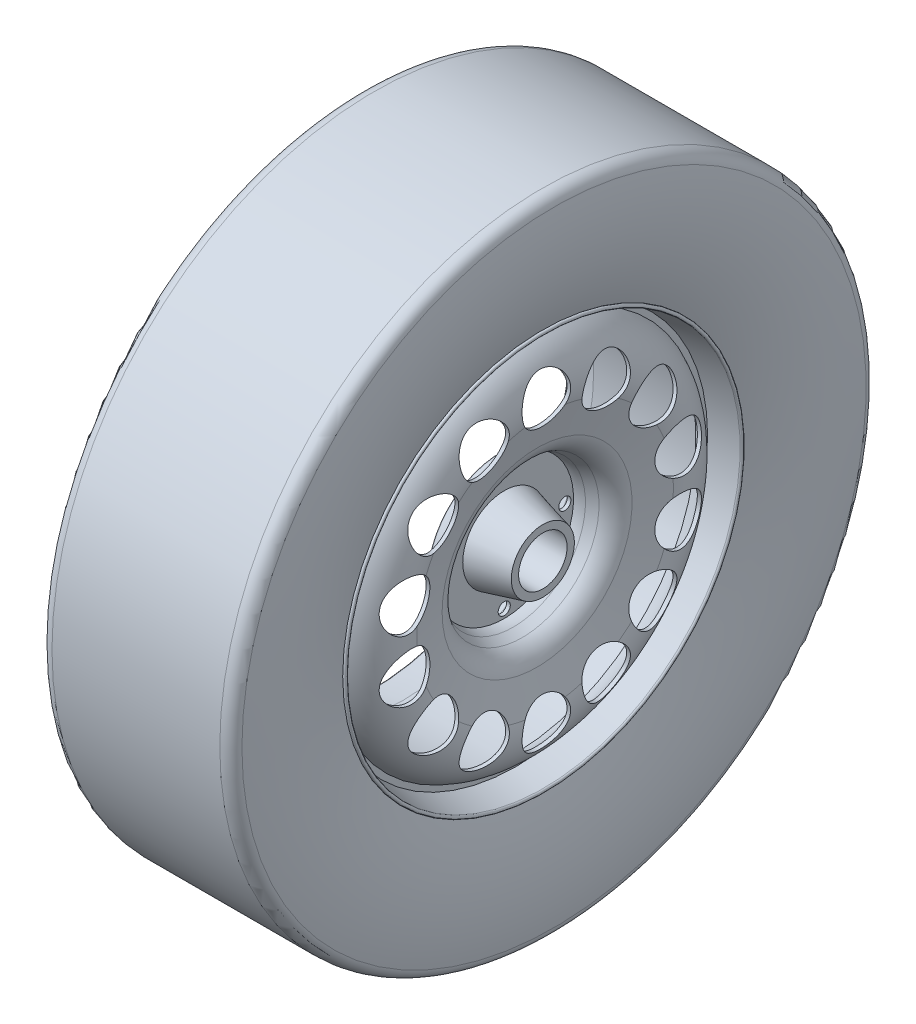
SolidWorks part; units mm, degrees
ref_plane "Front Plane" through (0, 0, 0) normal (0, 0, 1) x (1, 0, 0)
ref_plane "Top Plane" through (0, 0, 0) normal (0, 1, 0) x (1, 0, 0)
ref_plane "Right Plane" through (0, 0, 0) normal (1, 0, 0) x (0, 0, -1)
sketch "Sketch1" plane through (0, 0, 0) normal (1, 0, 0) x (0, 0, -1)
  circle A0 centre (0, 0) radius 165.1
  circle A1 centre (0, 0) radius 50
  circle A2 centre (0, 50) radius 5
  circle A3 centre (50, 0) radius 5
  circle A4 centre (0, -50) radius 5
  circle A5 centre (-50, 0) radius 5
  point P15 (0, 0)
  dimension "D1" = 330.2
  dimension "D2" = 100
  dimension "D3" = 10
  dimension "D4" = 4
sketch "Sketch2" plane through (0, 0, 0) normal (0, 0, 1) x (1, 0, 0)
  line L0 (35, 165.1) -> (35, -165.1) construction
  line L1 (0, -165.1) -> (0, 165.1) construction
  line L2 (0, 0) -> (69.85, 0) construction
  line L3 (0, -165.1) -> (0, 165.1) construction
  line L4 (69.85, -165.1) -> (69.85, 165.1) construction
  line L5 (-69.85, -165.1) -> (-69.85, 165.1) construction
  line L6 (35, 0) -> (35, 60)
  line L7 (-69.85, 165.1) -> (-44.85, 160)
  line L8 (-44.85, 160) -> (44.85, 160)
  line L9 (44.85, 160) -> (69.85, 165.1)
  line L10 (-70.4496, 162.1605) -> (-45.1529, 157)
  line L11 (-45.1529, 157) -> (45.1529, 157)
  line L12 (45.1529, 157) -> (70.4496, 162.1605)
  line L13 (35, 60) -> (35.2786, 60)
  line L14 (45.1529, 157) -> (45.1529, 151)
  line L15 (35, 20) -> (69.85, 20)
  line L16 (69.85, 20) -> (69.85, 26)
  line L17 (69.85, 26) -> (35, 35)
  line L18 (44.2229, 62.1115) -> (51.6796, 65.8398)
  line L19 (62.179, 79.0436) -> (68.7925, 106.4925)
  line L20 (48.1529, 157.612) -> (48.1529, 153.0235)
  line L21 (65.0955, 78.3409) -> (71.709, 105.7898)
  line L22 (45.5646, 59.4282) -> (53.0213, 63.1565)
  line L23 (38, 57.1616) -> (38, 57.1616)
  line L24 (38, 0) -> (38, 57.1616)
  line L25 (35, 23) -> (66.85, 23)
  line L26 (66.85, 23) -> (66.85, 23.6763)
  line L27 (66.85, 23.6763) -> (34.2499, 32.0953)
  line L28 (48.1529, 157) -> (48.1529, 153.0235) construction
  line L29 (0, 165.1) -> (0, 265.85) construction
  line L30 (-69.2005, 265.85) -> (69.2005, 265.85)
  arc A0 (69.85, 165.1) -> (70.4496, 162.1605) centre (70.1498, 163.6303) cw
  arc A1 (-69.85, 165.1) -> (-70.4496, 162.1605) centre (-70.1498, 163.6303) ccw
  arc A2 (45.1529, 151) -> (68.7925, 106.4925) centre (31.8381, 115.3963) cw
  arc A3 (51.6796, 65.8398) -> (62.179, 79.0436) centre (42.7354, 83.7284) ccw
  arc A4 (35.2786, 60) -> (44.2229, 62.1115) centre (35.2786, 80) ccw
  arc A5 (48.1529, 153.0235) -> (71.709, 105.7898) centre (31.8381, 115.3963) cw
  arc A6 (53.0213, 63.1565) -> (65.0955, 78.3409) centre (42.7354, 83.7284) ccw
  arc A7 (38, 57.1616) -> (45.5646, 59.4282) centre (35.2786, 80) ccw
  arc A8 (79.0707, 257.4556) -> (69.85, 165.1) centre (-98.5941, 228.5555) cw
  arc A9 (-79.0707, 257.4556) -> (-69.85, 165.1) centre (98.5941, 228.5555) ccw
  arc A10 (-69.2005, 265.85) -> (-79.0707, 257.4556) centre (-69.2005, 255.85) ccw
  arc A11 (69.2005, 265.85) -> (79.0707, 257.4556) centre (69.2005, 255.85) cw
  point P7 (35, 0)
  point P10 (0, 0)
  point P14 (69.85, 0)
  point P38 (60, 70)
  point P41 (40, 60)
  point P62 (0, 265.85)
  point P66 (-77.5, 265.85)
  point P69 (77.5, 265.85)
  dimension "D9" = 6
  dimension "D15" = 36.4925
  dimension "D17" = 20
  dimension "D22" = 180
  dimension "D23" = 180
  dimension "D24" = 10
  dimension "D1" = 35
  dimension "D2" = 330.2
  dimension "D3" = 69.85
  dimension "D4" = 60
  dimension "D5" = 160
  dimension "D6" = 25
  dimension "D7" = 25
  dimension "D8" = 3
  dimension "D10" = 6
  dimension "D11" = 15
  dimension "D12" = 20
  dimension "D13" = 5
  dimension "D14" = 10
  dimension "D16" = 20
  dimension "D19" = 3
  dimension "D20" = 155
  dimension "D21" = 100.75
  dimension "D18" = 3
revolve "Revolve1" add sketch "Sketch2" angle 360 about L2 region at (36.5, 21.5, 0) region at (38.3488, 21.5, 0) region at (36.5, 33.0634, 0) region at (36.2906, 47.5, 0) region at (0, 159.5005, 0)
revolve "Revolve2" add sketch "Sketch2<4>" angle 360 about L2 region at (0, 214.2856, 0)
sketch "Sketch2<4>" plane through (0, 0, 0) normal (0, 0, 1) x (1, 0, 0) same geometry as "Sketch2"
extrude "Cut-Extrude1" cut sketch "Sketch1" against normal through all both and the other way through all contours A1 A2 | A1 A2 | A1 A5 | A1 A5 | A1 A4 | A1 A4 | A1 A3 | A1 A3 region at (0, 0, -47.8335) region at (0, 0, -52.0764) region at (0, 47.8335, 0) region at (0, 52.0764, 0) region at (0, -52.0764, 0) region at (0, -47.8335, 0) region at (0, 0, 47.8335) region at (0, 0, 52.0764)
sketch "Sketch3" plane through (0, 0, 0) normal (1, 0, 0) x (0, 0, -1)
  circle A0 centre (0, 0) radius 153.0235 construction
  circle A1 centre (0, 0) radius 153.0235
  circle A2 centre (0, 0) radius 78.3409 construction
  circle A3 centre (0, 0) radius 78.3409
  circle A4 centre (0, 0) radius 115.7
  circle A5 centre (0, 115.7) radius 20
  dimension "D1" = 306.047
  dimension "D2" = 156.6819
  dimension "D3" = 231.4
  dimension "D4" = 40
extrude "Cut-Extrude3" cut sketch "Sketch3" against normal through all both and the other way through all contours A4 A5 | A4 A5 region at (0, 106.908, 0) region at (0, 123.8693, 0)
pattern_circular "CirPattern1" count 14 over 360 about axis through (69.85, 0, 0) along (-1, 0, 0) of "Cut-Extrude3"
